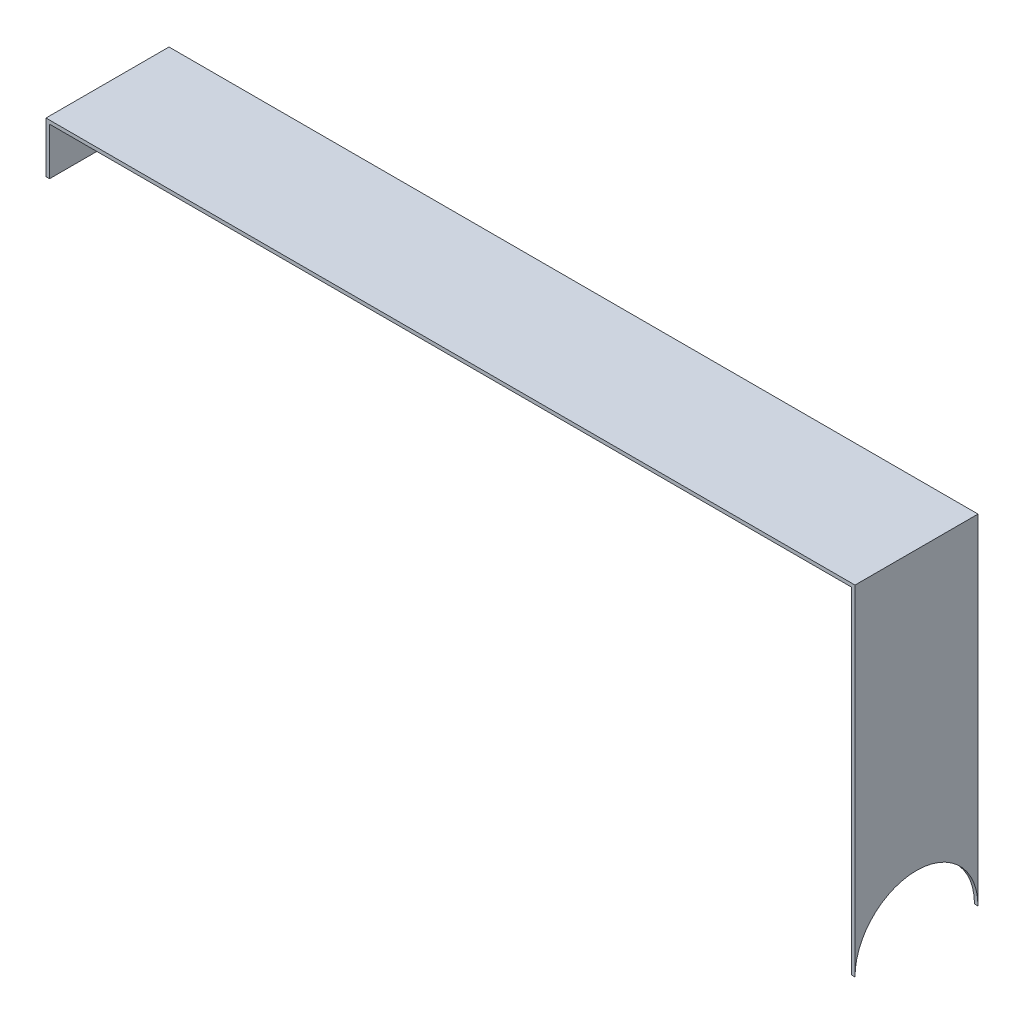
SolidWorks part; units mm, degrees
ref_plane "前视基准面" through (0, 0, 0) normal (0, 0, 1) x (1, 0, 0)
ref_plane "上视基准面" through (0, 0, 0) normal (0, 1, 0) x (1, 0, 0)
ref_plane "右视基准面" through (0, 0, 0) normal (1, 0, 0) x (0, 0, -1)
sketch "草图1" plane through (0, 0, 0) normal (0, 0, 1) x (1, 0, 0)
  line L1 (-37.8451, 44.347) -> (206.1549, 44.347)
  line L2 (206.1549, 44.347) -> (291.1549, 44.347)
  line L3 (291.1549, 44.347) -> (291.1549, -97.653)
  line L4 (291.1549, -97.653) -> (292.6549, -97.653)
  line L5 (292.6549, -97.653) -> (292.6549, 45.847)
  line L10 (-49.3451, 45.847) -> (-49.3451, 24.347)
  line L11 (-49.3451, 24.347) -> (-47.8451, 24.347)
  line L12 (292.6549, 45.847) -> (-49.3451, 45.847)
  line L14 (-37.8451, 44.347) -> (-47.8451, 44.347)
  line L15 (-47.8451, 44.347) -> (-47.8451, 24.347)
extrude "凸台-拉伸1" add sketch "草图1" along normal blind 52
sketch "草图2" plane through (291.1549, 0, 0) normal (-1, 0, 0) x (0, 0, 1)
  line L0 (52, -97.653) -> (0, -97.653) construction
  circle A0 centre (26, -97.653) radius 26
extrude "切除-拉伸1" cut sketch "草图2" against normal blind 52
